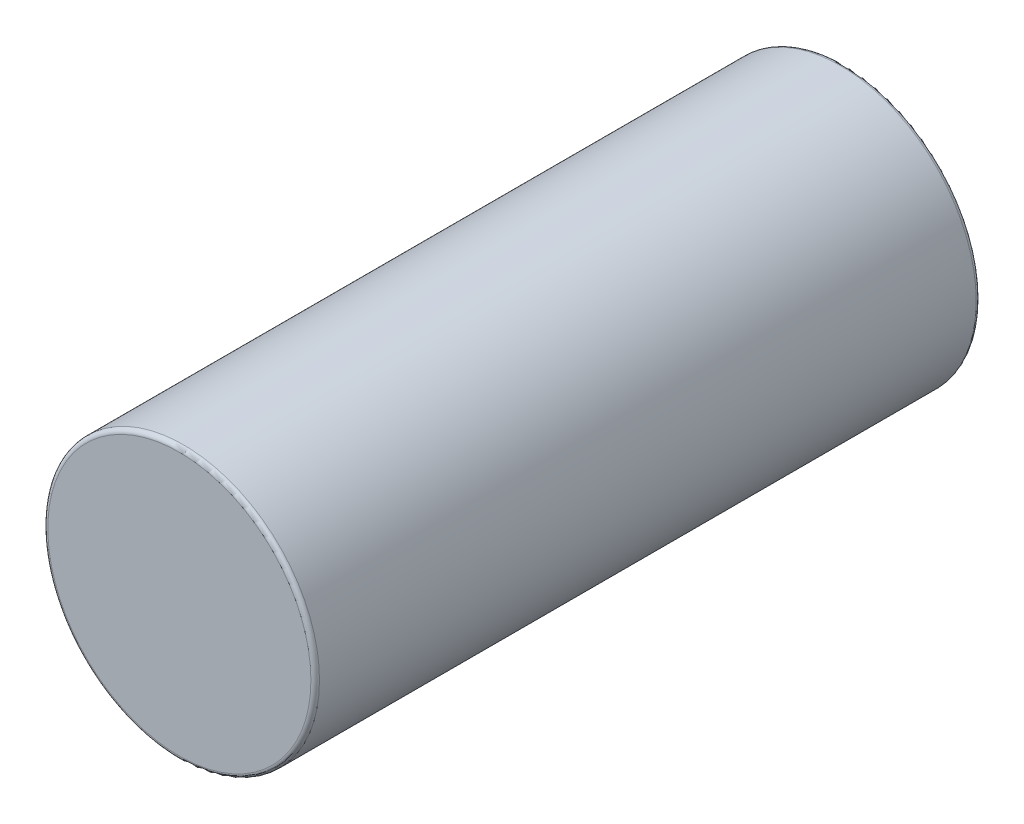
SolidWorks part; units mm, degrees
ref_plane "Front Plane" through (0, 0, 0) normal (0, 0, 1) x (1, 0, 0)
ref_plane "Top Plane" through (0, 0, 0) normal (0, 1, 0) x (1, 0, 0)
ref_plane "Right Plane" through (0, 0, 0) normal (1, 0, 0) x (0, 0, -1)
sketch "dia" plane through (0, 0, 0) normal (0, 0, 1) x (1, 0, 0)
  circle A0 centre (0, 0) radius 6.33
  dimension "D1" = 12.66
extrude "cycl" add sketch "dia" along normal blind 15.5 and the other way blind 15.5 contours A0
fillet "Fillet1" radius 0.2 2 edges at (6.33, 0, 15.5) (6.33, 0, -15.5)
sketch "center" plane through (0, 0, 0) normal (1, 0, 0) x (0, 0, -1)
  line L0 (-17.2907, 0) -> (21.5696, 0) construction
